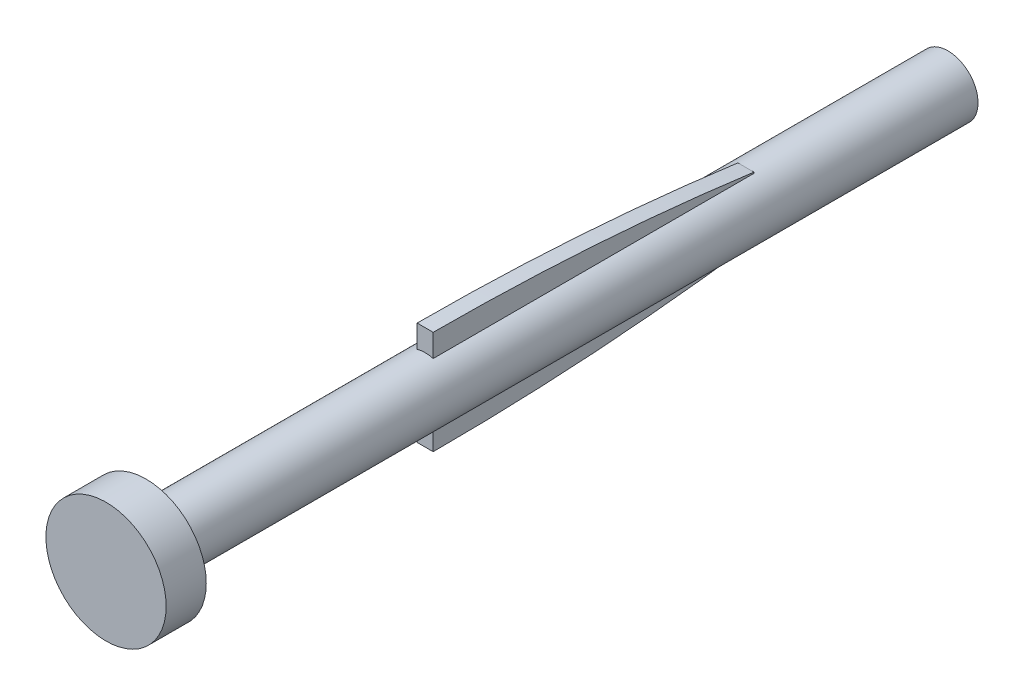
SolidWorks part; units mm, degrees
material "ABS"
ref_plane "Front Plane" through (0, 0, 0) normal (0, 0, 1) x (1, 0, 0)
ref_plane "Top Plane" through (0, 0, 0) normal (0, 1, 0) x (1, 0, 0)
ref_plane "Right Plane" through (0, 0, 0) normal (1, 0, 0) x (0, 0, -1)
sketch "Sketch1" plane through (0, 0, 0) normal (0, 0, 1) x (1, 0, 0)
  circle A0 centre (0, 0) radius 9.525
  dimension "D1" = 19.05
extrude "Boss-Extrude1" add sketch "Sketch1" along normal blind 6.35
sketch "Sketch2" plane through (0, 0, 0) normal (0, 0, -1) x (-1, 0, 0)
  line L1 (0, 0) -> (0, 4.7625) construction
  circle A3 centre (0, 0) radius 4.7625
  dimension "D1" = 4.7625
extrude "Boss-Extrude2" add sketch "Sketch2" along normal blind 127
sketch "Sketch3" plane through (0, 0, 0) normal (1, 0, 0) x (0, 0, -1)
  line L0 (0, 0) -> (44.196, 0) construction
  line L1 (44.196, -4.7625) -> (44.196, 4.7625)
  line L3 (44.196, 4.7625) -> (44.196, 8.1915)
  line L6 (94.996, 4.7625) -> (94.996, -4.7625)
  line L8 (44.196, 0) -> (94.996, 0) construction
  line L9 (44.196, 8.1915) -> (40.767, 8.1915) construction
  line L10 (40.767, 8.1915) -> (44.196, 4.7625) construction
  line L11 (44.196, -4.7625) -> (44.196, -8.1915)
  line L13 (127, 4.7625) -> (0, 4.7625) construction
  line L14 (44.196, 4.7625) -> (94.996, 4.7625) construction
  arc A0 (44.196, 8.1915) -> (94.996, 4.7625) centre (44.196, -369.8193) cw
  arc A1 (44.196, -8.1915) -> (94.996, -4.7625) centre (44.196, 369.8193) ccw
  dimension "D1" = 3.429
  dimension "D2" = 50.8
  dimension "D3" = 44.196
extrude "Boss-Extrude3" add sketch "Sketch3" along normal blind 1.27 and the other way blind 1.27
